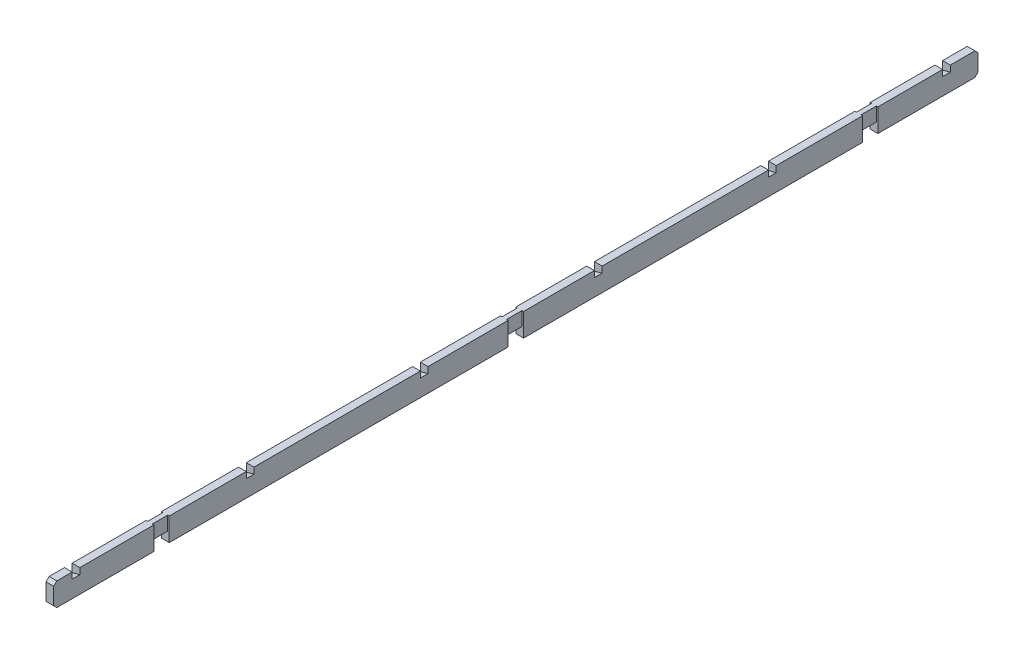
SolidWorks part; units mm, degrees
ref_plane "Front" through (0, 0, 0) normal (0, 0, 1) x (1, 0, 0)
ref_plane "Top" through (0, 0, 0) normal (0, 1, 0) x (1, 0, 0)
ref_plane "Right" through (0, 0, 0) normal (1, 0, 0) x (0, 0, -1)
sketch "Esquisse1" plane through (0, 0, 0) normal (0, 0, 1) x (1, 0, 0)
  line L1 (0, 0) -> (50, 0)
  line L2 (0, 0) -> (0, 150)
  line L3 (0, 150) -> (50, 150)
  line L4 (50, 0) -> (50, 150)
  dimension "D1" = 50
  dimension "D2" = 150
extrude "Boss.-Extru.1" add sketch "Esquisse1" along normal blind 6000
sketch "Esquisse2" plane through (0, 0, 6000) normal (0, 0, 1) x (1, 0, 0)
  line L0 (0, 96.6025) -> (50, 110)
  line L1 (0, 150) -> (0, 0) construction
  line L2 (50, 0) -> (50, 150) construction
  line L3 (50, 110) -> (50, 150)
  line L4 (50, 150) -> (0, 150)
  line L5 (0, 150) -> (0, 96.6025)
  point P8 (0, 97.3905)
  dimension "D1" = 40
  dimension "D2" = 75
extrude "Enlèv. mat.-Extru.1" cut sketch "Esquisse2" against normal blind 50 from offset 120 offset against normal yes
pattern_linear "Répétition linéaire1" count 6 spacing 1130 along (0, 0, -1) of "Enlèv. mat.-Extru.1"
chamfer "Chanfrein1" distance 20 angle 45 4 edges at (25, 0, 6000) (25, 150, 6000) (25, 0, 0) (25, 150, 0)
sketch "Esquisse3" plane through (0, 0, 0) normal (-1, 0, 0) x (0, 0, 1)
  line L0 (3000, 0) -> (3000, 150) construction
  line L1 (5980, 0) -> (20, 0) construction
  line L2 (3570, 150) -> (2490, 150) construction
  line L3 (1310, 150) -> (230, 150) construction
  line L4 (650, 150) -> (750, 150)
  line L5 (650, 150) -> (650, 0)
  line L6 (650, 0) -> (750, 0)
  line L7 (750, 150) -> (750, 0)
  line L8 (3050, 150) -> (2950, 150)
  line L9 (2950, 150) -> (2950, 0)
  line L10 (2950, 0) -> (3050, 0)
  line L11 (3050, 150) -> (3050, 0)
  line L12 (5250, 150) -> (5250, 0)
  line L13 (5350, 0) -> (5250, 0)
  line L14 (5350, 150) -> (5350, 0)
  line L15 (5350, 150) -> (5250, 150)
  dimension "D1" = 100
  dimension "D2" = 2300
extrude "Enlèv. mat.-Extru.2" cut sketch "Esquisse3" against normal blind 10
extrude "Enlèv. mat.-Extru.3" cut sketch "Esquisse3<2>" along normal blind 10 from vertex starting at point (50, 150, 20)
sketch "Esquisse3<2>" plane through (0, 0, 0) normal (-1, 0, 0) x (0, 0, 1) same geometry as "Esquisse3"
sketch "Esquisse4" plane through (10, 0, 0) normal (-1, 0, 0) x (0, 0, 1)
  line L0 (750, 0) -> (750, 150) construction
  line L1 (650, 0) -> (750, 0)
  line L2 (650, 0) -> (650, 60)
  line L3 (650, 60) -> (750, 60)
  line L4 (750, 0) -> (750, 60)
  line L5 (3050, 0) -> (3050, 150) construction
  line L6 (2950, 0) -> (3050, 0)
  line L7 (2950, 0) -> (2950, 60)
  line L8 (2950, 60) -> (3050, 60)
  line L9 (3050, 0) -> (3050, 60)
  line L10 (5350, 0) -> (5350, 150) construction
  line L11 (5250, 0) -> (5350, 0)
  line L12 (5250, 0) -> (5250, 60)
  line L13 (5250, 60) -> (5350, 60)
  line L14 (5350, 0) -> (5350, 60)
  dimension "D1" = 60
extrude "Enlèv. mat.-Extru.4" cut sketch "Esquisse4" against normal through all
